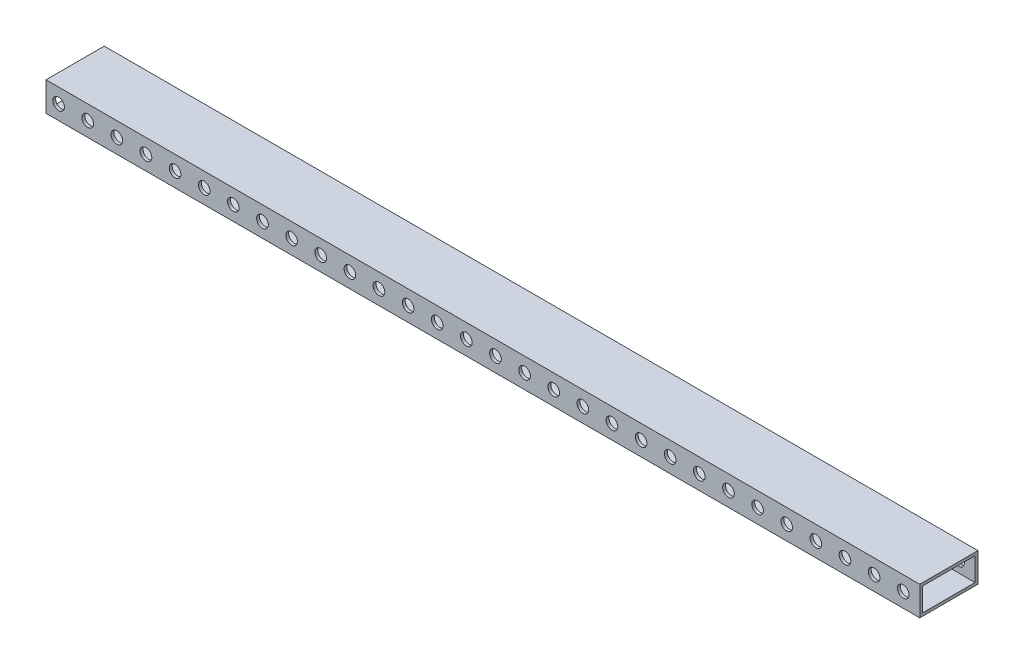
SolidWorks part; units mm, degrees
ref_plane "Front Plane" through (0, 0, 0) normal (0, 0, 1) x (1, 0, 0)
ref_plane "Top Plane" through (0, 0, 0) normal (0, 1, 0) x (1, 0, 0)
ref_plane "Right Plane" through (0, 0, 0) normal (1, 0, 0) x (0, 0, -1)
sketch "Sketch3" plane through (0, 0, 0) normal (1, 0, 0) x (0, 0, -1)
  line L0 (-17.5388, 8.1604) -> (28.1812, 8.1604)
  line L1 (-20.0788, 10.7004) -> (30.7212, 10.7004)
  line L2 (-20.0788, 10.7004) -> (-20.0788, -14.6996)
  line L3 (-20.0788, -14.6996) -> (30.7212, -14.6996)
  line L4 (30.7212, 10.7004) -> (30.7212, -14.6996)
  line L5 (28.1812, 8.1604) -> (28.1812, -12.1596)
  line L6 (-17.5388, -12.1596) -> (28.1812, -12.1596)
  line L7 (-17.5388, 8.1604) -> (-17.5388, -12.1596)
  dimension "D1" = 50.8
  dimension "D3" = 25.4
  dimension "D2" = 2.54
extrude "Boss-Extrude1" add sketch "Sketch3" along normal blind 762 contours L2 L1 L4 L3 | L0 L5 L6 L7
sketch "Sketch5" plane through (0, 0, 20.0788) normal (0, 0, 1) x (1, 0, 0)
  line L0 (762, 10.7004) -> (0, 10.7004) construction
  circle A0 centre (10.9788, -1.9996) radius 5.08
  circle A1 centre (36.3788, -1.9996) radius 5.08
  circle A2 centre (61.7788, -1.9996) radius 5.08
  circle A3 centre (87.1788, -1.9996) radius 5.08
  circle A4 centre (112.5788, -1.9996) radius 5.08
  circle A5 centre (137.9788, -1.9996) radius 5.08
  circle A6 centre (163.3788, -1.9996) radius 5.08
  circle A7 centre (188.7788, -1.9996) radius 5.08
  circle A8 centre (214.1788, -1.9996) radius 5.08
  circle A9 centre (239.5788, -1.9996) radius 5.08
  circle A10 centre (264.9788, -1.9996) radius 5.08
  circle A11 centre (290.3788, -1.9996) radius 5.08
  circle A12 centre (315.7788, -1.9996) radius 5.08
  circle A13 centre (341.1788, -1.9996) radius 5.08
  circle A14 centre (366.5788, -1.9996) radius 5.08
  circle A15 centre (391.9788, -1.9996) radius 5.08
  circle A16 centre (417.3788, -1.9996) radius 5.08
  circle A17 centre (442.7788, -1.9996) radius 5.08
  circle A18 centre (468.1788, -1.9996) radius 5.08
  circle A19 centre (493.5788, -1.9996) radius 5.08
  circle A20 centre (518.9788, -1.9996) radius 5.08
  circle A21 centre (544.3788, -1.9996) radius 5.08
  circle A22 centre (569.7788, -1.9996) radius 5.08
  circle A23 centre (595.1788, -1.9996) radius 5.08
  circle A24 centre (620.5788, -1.9996) radius 5.08
  circle A25 centre (645.9788, -1.9996) radius 5.08
  circle A26 centre (671.3788, -1.9996) radius 5.08
  circle A27 centre (696.7788, -1.9996) radius 5.08
  circle A28 centre (722.1788, -1.9996) radius 5.08
  circle A29 centre (747.5788, -1.9996) radius 5.08
  point P4 (0, 0)
  point P63 (0, 0)
  point P64 (0, 0)
  point P65 (0, 0)
  point P66 (0, 0)
  point P67 (0, 0)
  dimension "D1" = 12.7
  dimension "D2" = 28
  dimension "D3" = 3
extrude "Cut-Extrude2" cut sketch "Sketch5" against normal blind 127 contours A0 | A1 | A3 | A2 | A4 | A6 | A5 | A7 | A8 | A9 | A10 | A11 | A12 | A13 | A14 | A15 | A16 | A17 | A19 | A20 | A18 | A21 | A22 | A23 | A24 | A26 | A27 | A25
sketch "Sketch6" plane through (0, 0, 20.0788) normal (0, 0, 1) x (1, 0, 0)
extrude "Cut-Extrude5" cut sketch "Sketch5<8>" against normal blind 127 contours A28
sketch "Sketch5<8>" plane through (0, 0, 20.0788) normal (0, 0, 1) x (1, 0, 0) same geometry as "Sketch5"
extrude "Cut-Extrude6" cut sketch "Sketch5<9>" against normal blind 127 contours A29
sketch "Sketch5<9>" plane through (0, 0, 20.0788) normal (0, 0, 1) x (1, 0, 0) same geometry as "Sketch5"
